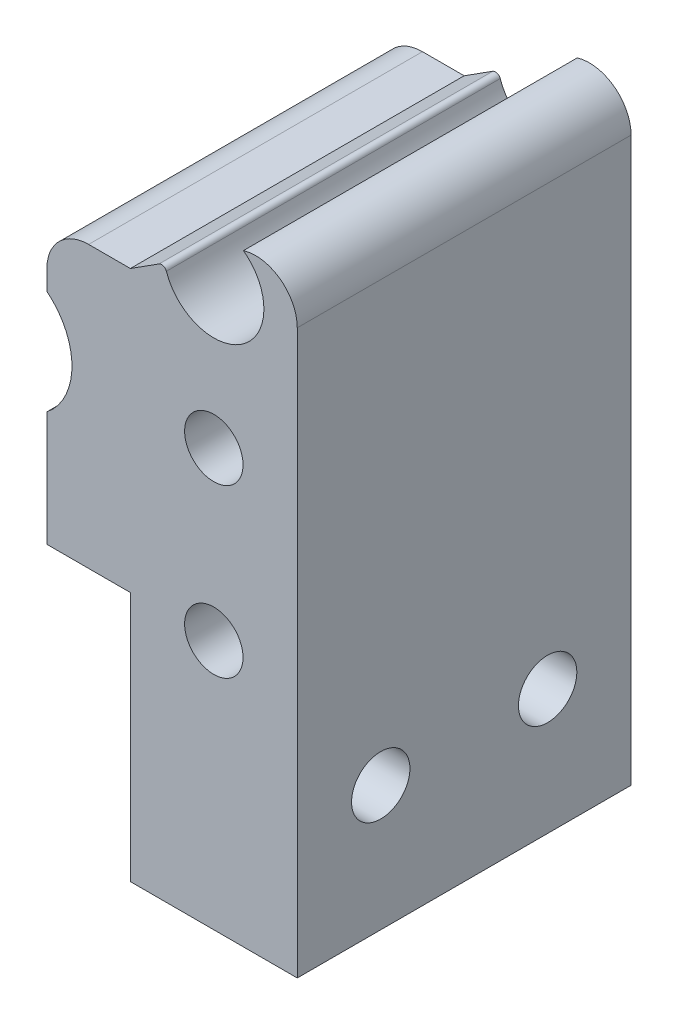
SolidWorks part; units mm, degrees
material "ABS"
ref_plane "Front Plane" through (0, 0, 0) normal (0, 0, 1) x (1, 0, 0)
ref_plane "Top Plane" through (0, 0, 0) normal (0, 1, 0) x (1, 0, 0)
ref_plane "Right Plane" through (0, 0, 0) normal (1, 0, 0) x (0, 0, -1)
sketch "Sketch2" plane through (0, 0, 0) normal (0, 0, 1) x (1, 0, 0)
  line L0 (0, 0) -> (0, 15)
  line L1 (0, 31.8146) -> (10, 38.1854)
  line L2 (0, 24.91) -> (0, 38.1505) construction
  line L3 (0, 15) -> (0, 31.8146) construction
  line L4 (10, 38.1854) -> (10, 0)
  line L5 (10, 0) -> (0, 0)
  line L6 (0, 31.8146) -> (-5, 31.8146)
  line L7 (0, 31.8146) -> (0, 15) construction
  line L8 (0, 15) -> (-5, 15)
  line L9 (-5, 31.8146) -> (-5, 15)
  point P4 (5, 35)
  dimension "D4" = 5
  dimension "D5" = 20
  dimension "D1" = 15
  dimension "D2" = 57.5
  dimension "D3" = 10
extrude "Boss-Extrude1" add sketch "Sketch2" along normal blind 20 contours L1 L0 L5 L4 region at (3.6697, 18.6831, 0)
sketch "Sketch3" plane through (10, 0, 0) normal (1, 0, 0) x (0, 0, -1)
  line L0 (-20, 7.5) -> (0, 7.5) construction
  line L1 (-20, 38.1854) -> (-20, 0) construction
  line L2 (0, 38.1854) -> (0, 0) construction
  line L3 (-20, 0) -> (0, 0) construction
  line L4 (-10, 7.5) -> (-10, 0) construction
  circle A0 centre (-15, 7.5) radius 1.75
  circle A1 centre (-5, 7.5) radius 1.75
  dimension "D2" = 3.5
  dimension "D3" = 3.5
  dimension "D1" = 7.5
  dimension "D4" = 5
  dimension "D5" = 5
extrude "Cut-Extrude1" cut sketch "Sketch3" against normal through all
sketch "Sketch4" plane through (0, 0, 20) normal (0, 0, 1) x (1, 0, 0)
  line L0 (0, 15) -> (-5, 15) construction
  line L1 (0, 0) -> (0, 15) construction
  line L2 (5, 0) -> (5, 25) construction
  line L4 (10, 0) -> (0, 0) construction
  circle A0 centre (5, 33.71) radius 3
  circle A1 centre (5, 25) radius 1.75
  circle A2 centre (-7.5, 25) radius 4
  circle A3 centre (5, 15) radius 1.75
  dimension "D1" = 6
  dimension "D2" = 18.71
  dimension "D3" = 5
  dimension "D4" = 3.5
  dimension "D5" = 25
  dimension "D6" = 8
  dimension "D7" = 7.5
  dimension "D8" = 15
extrude "Cut-Extrude2" cut sketch "Sketch4" against normal through all
fillet "Fillet2" radius 2.5 2 edges at (10, 38.1854, 10) (-5, 31.8146, 10)
fillet "Fillet3" radius 0.3 1 edges at (2.0575, 33.1254, 10)
